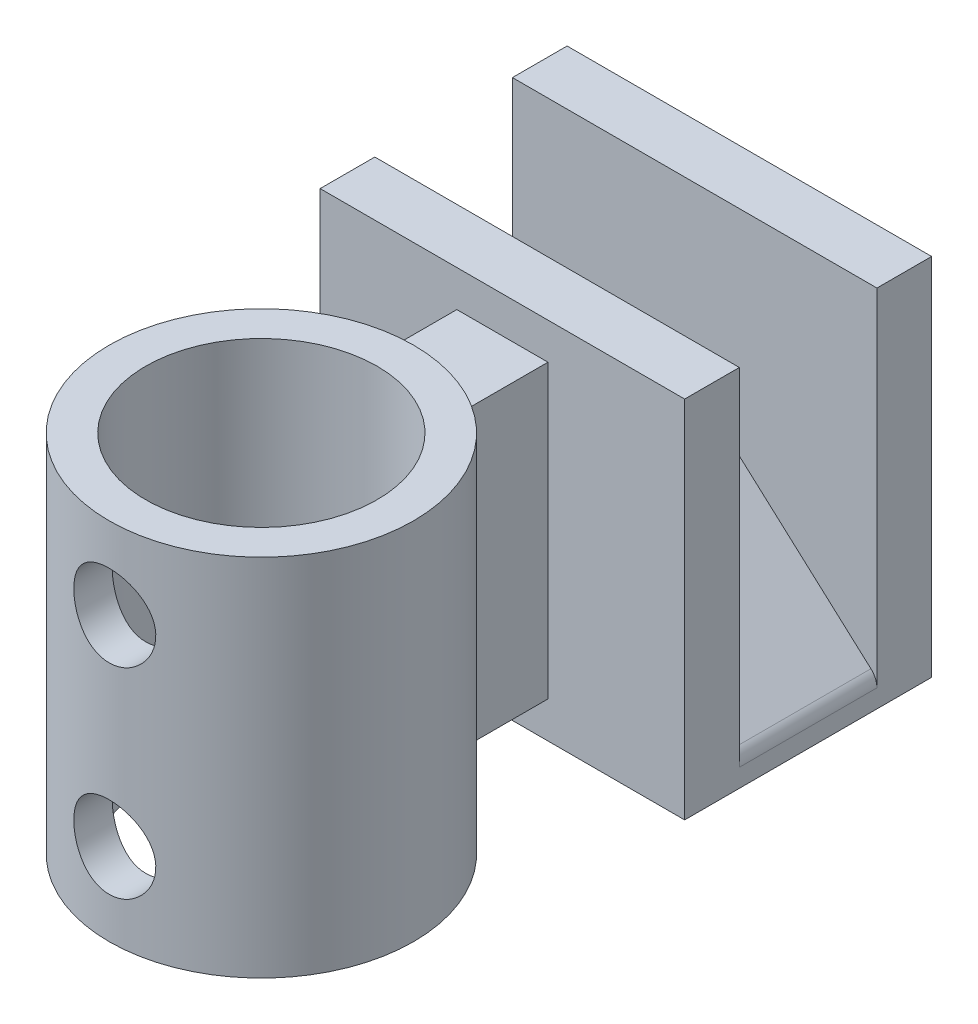
SolidWorks part; units mm, degrees
ref_plane "Front Plane" through (0, 0, 0) normal (0, 0, 1) x (1, 0, 0)
ref_plane "Top Plane" through (0, 0, 0) normal (0, 1, 0) x (1, 0, 0)
ref_plane "Right Plane" through (0, 0, 0) normal (1, 0, 0) x (0, 0, -1)
sketch "Sketch2" plane through (0, 0, 0) normal (0, 0, 1) x (1, 0, 0)
  line L1 (-10, -5) -> (10, -5)
  line L2 (-10, -5) -> (-10, 5)
  line L3 (-10, 5) -> (10, 5)
  line L4 (10, -5) -> (10, 5)
  line L5 (-10, -5) -> (10, 5) construction
  line L6 (-10, 5) -> (10, -5) construction
  point P0 (0, 0)
  dimension "D1" = 10
  dimension "D2" = 20
extrude "Boss-Extrude1" add sketch "Sketch2" along normal mid plane 7.55
chamfer "Chamfer1" distance 9.5 angle 42 2 edges at (10, 5, 0) (-10, 5, 0) first distance on face at (0, 5, 0)
fillet "Fillet3" radius 1 4 edges at (-10, -3.5538, 0) (10, -3.5538, 0) (0.5, 5, 0) (-0.5, 5, 0)
sketch "Sketch3" plane through (0, 0, 3.775) normal (0, 0, 1) x (1, 0, 0)
  line L0 (-10, -5) -> (10, -5) construction
  line L1 (-10, 15) -> (10, 15)
  line L2 (-10, 15) -> (-10, -5)
  line L3 (-10, -5) -> (10, -5)
  line L4 (10, 15) -> (10, -5)
  line L5 (-10, 15) -> (10, -5) construction
  line L6 (-10, -5) -> (10, 15) construction
  point P0 (0, 5)
  dimension "D1" = 20
  dimension "D2" = 20
extrude "Boss-Extrude2" add sketch "Sketch3" along normal blind 3
mirror "Mirror1" about plane through (0, 0, 0) normal (0, 0, 1) of "Boss-Extrude2"
sketch "Sketch6" plane through (0, 0, 0) normal (0, 1, 0) x (1, 0, 0)
  circle A0 centre (0, -20) radius 6.35
  circle A1 centre (0, -20) radius 8.35
  dimension "D1" = 12.7
  dimension "D2" = 2
  dimension "D3" = 20
extrude "Boss-Extrude3" add sketch "Sketch6" along normal up to surface and the other way up to surface separate body up to face at (0, 15, 5.275) other way up to face at (0, -5, 0)
sketch "Sketch5" plane through (0, 0, 6.775) normal (0, 0, 1) x (1, 0, 0)
  line L0 (-10, -5) -> (10, -5) construction
  line L1 (-2.5, 13) -> (2.5, 13)
  line L2 (-2.5, 13) -> (-2.5, -3)
  line L3 (-2.5, -3) -> (2.5, -3)
  line L4 (2.5, 13) -> (2.5, -3)
  line L5 (-2.5, 13) -> (2.5, -3) construction
  line L6 (-2.5, -3) -> (2.5, 13) construction
  line L7 (10, 15) -> (-10, 15) construction
  point P0 (0, 5)
  dimension "D1" = 2
  dimension "D2" = 2
  dimension "D3" = 5
extrude "Boss-Extrude4" add sketch "Sketch5" along normal up to surface (5.258 mm away) up to face at (0, 15, 11.65)
ref_plane "Plane1" through (0, 0, 20) normal (0, 0, 1) x (1, 0, 0)
sketch "Sketch7" plane through (0, 0, 20) normal (0, 0, 1) x (1, 0, 0)
  line L0 (-8.35, -5) -> (8.35, -5) construction
  line L1 (6.35, 15) -> (-6.35, 15) construction
  circle A0 centre (0, 10.5) radius 2.25
  circle A1 centre (0, -0.5) radius 2.25
  dimension "D1" = 4.5
  dimension "D2" = 4.5
  dimension "D3" = 4.5
  dimension "D4" = 4.5
extrude "Cut-Extrude1" cut sketch "Sketch7" along normal up to surface (8.0412 mm away) up to face at (0, 15, 11.65)
